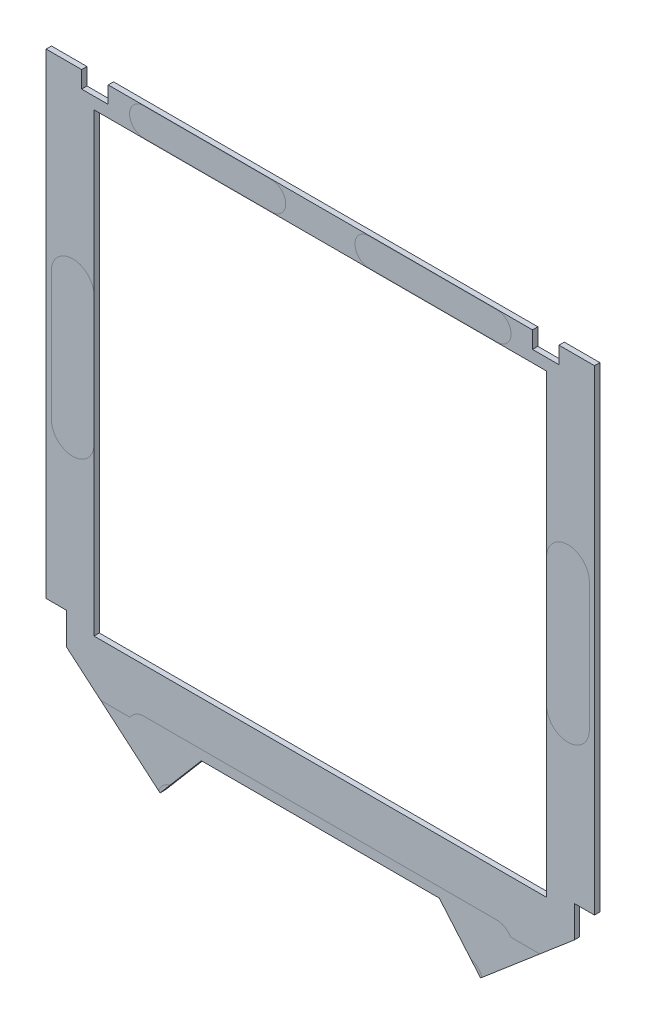
SolidWorks part; units mm, degrees
ref_plane "Front" through (0, 0, 0) normal (0, 0, 1) x (1, 0, 0)
ref_plane "Top" through (0, 0, 0) normal (0, 1, 0) x (1, 0, 0)
ref_plane "Right" through (0, 0, 0) normal (1, 0, 0) x (0, 0, -1)
sketch "Sketch1" plane through (0, 0, -8.9364) normal (0, 0, 1) x (1, 0, 0)
  line L0 (-62.992, 192.0875) -> (62.992, 192.0875)
  line L1 (-66.675, 183.0705) -> (66.675, 183.0705) construction
  line L2 (-66.675, 48.768) -> (66.675, 48.768) construction
  line L3 (-66.675, 48.768) -> (66.675, 48.768) construction
  line L4 (66.675, 183.0705) -> (66.675, 48.768) construction
  line L5 (62.992, 192.0875) -> (62.992, 187.071)
  line L6 (62.992, 187.071) -> (70.866, 187.071)
  line L7 (70.866, 187.071) -> (70.866, 192.0875)
  line L8 (70.866, 192.0875) -> (81.407, 192.0875)
  line L9 (81.407, 192.0875) -> (81.407, 50.8)
  line L10 (81.407, 50.8) -> (75.438, 50.8)
  line L11 (75.438, 50.8) -> (75.438, 41.4295)
  line L12 (75.438, 41.4295) -> (47.5845, 17.7206)
  line L13 (47.5845, 17.7206) -> (35.3184, 32.131)
  line L14 (35.3184, 32.131) -> (-35.3184, 32.131)
  line L15 (-67.183, 183.5785) -> (67.183, 183.5785)
  line L16 (67.183, 183.5785) -> (67.183, 48.26)
  line L17 (-67.183, 48.26) -> (67.183, 48.26)
  line L18 (-67.183, 48.26) -> (67.183, 48.26) construction
  line L19 (81.915, 162.3536) -> (81.915, 172.6784) construction
  line L20 (0, 194.183) -> (0, 11.7602) construction
  line L22 (46.5936, 16.2101) -> (78.9144, 43.7216) construction
  line L23 (-67.183, 183.5785) -> (67.183, 183.5785) construction
  line L24 (-66.675, 183.0705) -> (66.675, 183.0705) construction
  line L25 (-66.675, 183.0705) -> (-66.675, 48.768) construction
  line L26 (-67.183, 183.5785) -> (-67.183, 48.26) construction
  line L27 (33.1388, 192.5955) -> (24.7732, 192.5955) construction
  line L28 (81.915, 192.5955) -> (69.6786, 192.5955) construction
  line L29 (-43.2308, 13.3477) -> (43.2308, 13.3477) construction
  line L34 (-66.675, 183.0705) -> (-66.675, 48.768) construction
  line L35 (-67.183, 183.5785) -> (-67.183, 48.26)
  line L36 (-47.5845, 17.7206) -> (-35.3184, 32.131)
  line L37 (-75.438, 41.4295) -> (-47.5845, 17.7206)
  line L38 (-75.438, 50.8) -> (-75.438, 41.4295)
  line L39 (-81.407, 50.8) -> (-75.438, 50.8)
  line L40 (-81.407, 192.0875) -> (-81.407, 50.8)
  line L41 (-70.866, 192.0875) -> (-81.407, 192.0875)
  line L42 (-70.866, 187.071) -> (-70.866, 192.0875)
  line L43 (-62.992, 187.071) -> (-70.866, 187.071)
  line L44 (-62.992, 192.0875) -> (-62.992, 187.071)
  circle A0 centre (79.375, 46.863) radius 3.937 construction
  circle A3 centre (43.434, 16.5227) radius 3.937 construction
  circle A5 centre (66.929, 191.008) radius 3.937 construction
  circle A7 centre (-66.929, 191.008) radius 3.937 construction
  circle A8 centre (-43.434, 16.5227) radius 3.937 construction
  circle A9 centre (-79.375, 46.863) radius 3.937 construction
  point P29 (0, 183.5785)
  point P30 (0, 183.0705)
  point P66 (0, 48.768)
  point P67 (0, 48.26)
  point P69 (0, 32.131)
  point P78 (0, 192.0875)
  dimension "D6" = 18.7833
  dimension "D1" = 0.508
  dimension "D2" = 0.508
  dimension "D3" = 0.508
  dimension "D4" = 0.508
  dimension "D5" = 0.508
extrude "Boss-Extrude1" add sketch "Sketch1" along normal blind 1.5875
sketch "Sketch2" plane through (0, 0, -7.3489) normal (0, 0, 1) x (1, 0, 0)
  line L2 (67.1735, 135.763) -> (67.1735, 97.663)
  line L3 (79.8735, 97.663) -> (79.8735, 135.763)
  line L4 (67.1735, 135.763) -> (67.1735, 97.663)
  line L5 (79.8735, 97.663) -> (79.8735, 135.763)
  line L6 (-67.1735, 97.663) -> (-67.1735, 135.763)
  line L7 (-79.8735, 135.763) -> (-79.8735, 97.663)
  line L8 (-67.1735, 97.663) -> (-67.1735, 135.763)
  line L9 (-79.8735, 135.763) -> (-79.8735, 97.663)
  line L14 (-57.15, 23.111) -> (-48.4599, 15.7139)
  line L15 (-56.4935, 32.7025) -> (-83.82, 32.7025)
  line L16 (52.3875, 35.052) -> (-52.3875, 35.052)
  line L17 (-56.4935, 32.7025) -> (-83.82, 32.7025)
  line L18 (48.4599, 15.7139) -> (57.15, 23.111)
  line L19 (-33.8657, 12.3825) -> (33.8657, 12.3825)
  line L20 (-57.15, 23.111) -> (-48.4599, 15.7139)
  line L22 (52.3875, 35.052) -> (-52.3875, 35.052)
  line L24 (48.4599, 15.7139) -> (57.15, 23.111)
  line L25 (-33.8657, 12.3825) -> (33.8657, 12.3825)
  line L40 (83.82, 32.7025) -> (56.4935, 32.7025)
  line L41 (83.82, 32.7025) -> (56.4935, 32.7025)
  line L42 (57.15, 23.111) -> (72.8121, 23.111)
  line L43 (57.15, 23.111) -> (72.8121, 23.111)
  line L44 (-72.8121, 23.111) -> (-57.15, 23.111)
  line L45 (-72.8121, 23.111) -> (-57.15, 23.111)
  line L52 (14.4145, 183.7055) -> (52.5145, 183.7055)
  line L53 (52.5145, 191.9605) -> (14.4145, 191.9605)
  line L54 (14.4145, 183.7055) -> (52.5145, 183.7055)
  line L55 (52.5145, 191.9605) -> (14.4145, 191.9605)
  line L56 (-14.4145, 191.9605) -> (-52.5145, 191.9605)
  line L57 (-52.5145, 183.7055) -> (-14.4145, 183.7055)
  line L58 (-14.4145, 191.9605) -> (-52.5145, 191.9605)
  line L59 (-52.5145, 183.7055) -> (-14.4145, 183.7055)
  arc A4 (73.5235, 91.313) -> (79.8735, 97.663) centre (73.5235, 97.663) ccw
  arc A5 (67.1735, 97.663) -> (73.5235, 91.313) centre (73.5235, 97.663) ccw
  arc A6 (73.5235, 142.113) -> (67.1735, 135.763) centre (73.5235, 135.763) ccw
  arc A7 (79.8735, 135.763) -> (73.5235, 142.113) centre (73.5235, 135.763) ccw
  arc A8 (73.5235, 91.313) -> (79.8735, 97.663) centre (73.5235, 97.663) ccw
  arc A9 (67.1735, 97.663) -> (73.5235, 91.313) centre (73.5235, 97.663) ccw
  arc A10 (73.5235, 142.113) -> (67.1735, 135.763) centre (73.5235, 135.763) ccw
  arc A11 (79.8735, 135.763) -> (73.5235, 142.113) centre (73.5235, 135.763) ccw
  arc A12 (-73.5235, 91.313) -> (-67.1735, 97.663) centre (-73.5235, 97.663) ccw
  arc A13 (-79.8735, 97.663) -> (-73.5235, 91.313) centre (-73.5235, 97.663) ccw
  arc A14 (-73.5235, 142.113) -> (-79.8735, 135.763) centre (-73.5235, 135.763) ccw
  arc A15 (-67.1735, 135.763) -> (-73.5235, 142.113) centre (-73.5235, 135.763) ccw
  arc A16 (-73.5235, 91.313) -> (-67.1735, 97.663) centre (-73.5235, 97.663) ccw
  arc A17 (-79.8735, 97.663) -> (-73.5235, 91.313) centre (-73.5235, 97.663) ccw
  arc A18 (-73.5235, 142.113) -> (-79.8735, 135.763) centre (-73.5235, 135.763) ccw
  arc A19 (-67.1735, 135.763) -> (-73.5235, 142.113) centre (-73.5235, 135.763) ccw
  arc A24 (-52.3875, 35.052) -> (-56.4935, 32.7025) centre (-52.3875, 30.2895) ccw
  arc A25 (56.4935, 32.7025) -> (52.3875, 35.052) centre (52.3875, 30.2895) ccw
  arc A26 (48.2498, 16.8359) -> (48.4599, 15.7139) centre (53.0023, 17.145) ccw
  arc A27 (48.2498, 16.8359) -> (38.6182, 16.8359) centre (43.434, 16.5227) ccw
  arc A28 (33.8657, 12.3825) -> (38.6182, 16.8359) centre (33.8657, 17.145) ccw
  arc A29 (-38.6182, 16.8359) -> (-33.8657, 12.3825) centre (-33.8657, 17.145) ccw
  arc A30 (-38.6182, 16.8359) -> (-48.2498, 16.8359) centre (-43.434, 16.5227) ccw
  arc A31 (-48.4599, 15.7139) -> (-48.2498, 16.8359) centre (-53.0023, 17.145) ccw
  arc A32 (-52.3875, 35.052) -> (-56.4935, 32.7025) centre (-52.3875, 30.2895) ccw
  arc A33 (56.4935, 32.7025) -> (52.3875, 35.052) centre (52.3875, 30.2895) ccw
  arc A34 (48.2498, 16.8359) -> (48.4599, 15.7139) centre (53.0023, 17.145) ccw
  arc A35 (48.2498, 16.8359) -> (38.6182, 16.8359) centre (43.434, 16.5227) ccw
  arc A36 (33.8657, 12.3825) -> (38.6182, 16.8359) centre (33.8657, 17.145) ccw
  arc A37 (-38.6182, 16.8359) -> (-33.8657, 12.3825) centre (-33.8657, 17.145) ccw
  arc A38 (-38.6182, 16.8359) -> (-48.2498, 16.8359) centre (-43.434, 16.5227) ccw
  arc A39 (-48.4599, 15.7139) -> (-48.2498, 16.8359) centre (-53.0023, 17.145) ccw
  arc A68 (-83.82, 32.7025) -> (-94.8574, 22.8799) centre (-83.82, 21.59) ccw
  arc A69 (-83.82, 32.7025) -> (-94.8574, 22.8799) centre (-83.82, 21.59) ccw
  arc A70 (72.7826, 20.3001) -> (83.82, 32.7025) centre (83.82, 21.59) ccw
  arc A71 (72.7826, 20.3001) -> (83.82, 32.7025) centre (83.82, 21.59) ccw
  arc A72 (72.7826, 22.8799) -> (72.7826, 20.3001) centre (74.2188, 21.59) ccw
  arc A73 (72.7826, 22.8799) -> (72.7826, 20.3001) centre (74.2188, 21.59) ccw
  arc A74 (72.8121, 23.111) -> (72.7826, 22.8799) centre (83.82, 21.59) ccw
  arc A75 (72.8121, 23.111) -> (72.7826, 22.8799) centre (83.82, 21.59) ccw
  arc A76 (-94.8574, 20.3001) -> (-72.8121, 23.111) centre (-83.82, 21.59) ccw
  arc A77 (-94.8574, 20.3001) -> (-72.8121, 23.111) centre (-83.82, 21.59) ccw
  arc A78 (-94.8574, 22.8799) -> (-94.8574, 20.3001) centre (-93.4212, 21.59) ccw
  arc A79 (-94.8574, 22.8799) -> (-94.8574, 20.3001) centre (-93.4212, 21.59) ccw
  arc A82 (14.4145, 191.9605) -> (14.4145, 183.7055) centre (14.4145, 187.833) ccw
  arc A83 (52.5145, 183.7055) -> (52.5145, 191.9605) centre (52.5145, 187.833) ccw
  arc A84 (14.4145, 191.9605) -> (14.4145, 183.7055) centre (14.4145, 187.833) ccw
  arc A85 (52.5145, 183.7055) -> (52.5145, 191.9605) centre (52.5145, 187.833) ccw
  arc A86 (-14.4145, 183.7055) -> (-14.4145, 191.9605) centre (-14.4145, 187.833) ccw
  arc A87 (-52.5145, 191.9605) -> (-52.5145, 183.7055) centre (-52.5145, 187.833) ccw
  arc A88 (-14.4145, 183.7055) -> (-14.4145, 191.9605) centre (-14.4145, 187.833) ccw
  arc A89 (-52.5145, 191.9605) -> (-52.5145, 183.7055) centre (-52.5145, 187.833) ccw
  dimension "D1" = 0
  dimension "D2" = 0
  dimension "D3" = 0
  dimension "D4" = 0
  dimension "D5" = 0
split line "Split Line1"
